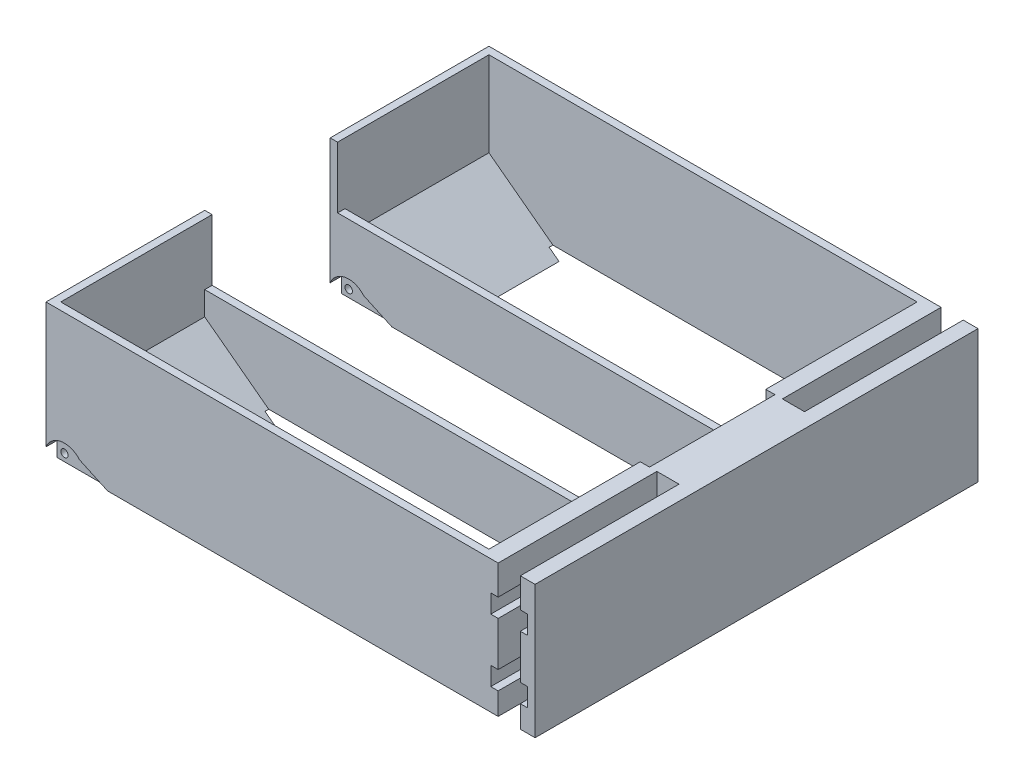
SolidWorks part; units mm, degrees
ref_plane "Front Plane" through (0, 0, 0) normal (0, 0, 1) x (1, 0, 0)
ref_plane "Top Plane" through (0, 0, 0) normal (0, 1, 0) x (1, 0, 0)
ref_plane "Right Plane" through (0, 0, 0) normal (1, 0, 0) x (0, 0, -1)
sketch "Sketch2" plane through (0, 0, 0) normal (0, 1, 0) x (1, 0, 0)
  line L1 (-60, -21.5) -> (60, -21.5)
  line L2 (-60, -21.5) -> (-60, 21.5)
  line L3 (-60, 21.5) -> (60, 21.5)
  line L4 (60, -21.5) -> (60, 21.5)
  line L5 (-60, -21.5) -> (60, 21.5) construction
  line L6 (-60, 21.5) -> (60, -21.5) construction
  point P0 (0, 0)
  dimension "D1" = 120
  dimension "D2" = 43
extrude "Boss-Extrude1" add sketch "Sketch2" along normal blind 38 contours L2 L3 L4 L1
sketch "Sketch3" plane through (0, 38, 0) normal (0, 1, 0) x (1, 0, 0)
  line L0 (-60, 21.5) -> (60, 21.5) construction
  line L1 (-58, -19.5) -> (58, -19.5)
  line L2 (-58, -19.5) -> (-58, 19.5)
  line L3 (-58, 19.5) -> (58, 19.5)
  line L4 (58, -19.5) -> (58, 19.5)
  line L5 (-58, -19.5) -> (58, 19.5) construction
  line L6 (-58, 19.5) -> (58, -19.5) construction
  line L7 (60, -21.5) -> (60, 21.5) construction
  point P0 (0, 0)
  dimension "D1" = 2
  dimension "D2" = 2
extrude "Cut-Extrude1" cut sketch "Sketch3" against normal up to vertex (38 mm away) up to point (-60, 0, -21.5)
sketch "Sketch4" plane through (0, 0, -19.5) normal (0, 0, 1) x (1, 0, 0)
  line L0 (-58, 0) -> (-58, 15)
  line L1 (-58, 15) -> (-38, 0)
  line L2 (-60, 0) -> (60, 0) construction
  line L3 (-38, 0) -> (-58, 0)
  dimension "D1" = 15
  dimension "D2" = 20
extrude "Boss-Extrude2" add sketch "Sketch4" along normal up to vertex (39 mm away) up to point (-58, 0, 19.5)
sketch "Sketch5" plane through (60, 0, 0) normal (1, 0, 0) x (0, 0, -1)
  line L1 (-21.5, 38) -> (21.5, 38)
  line L2 (-21.5, 38) -> (-21.5, 0)
  line L3 (-21.5, 0) -> (21.5, 0)
  line L4 (21.5, 38) -> (21.5, 0)
extrude "Boss-Extrude3" add sketch "Sketch5" along normal blind 2.5
sketch "Sketch6" plane through (0, 0, -21.5) normal (0, 0, -1) x (-1, 0, 0)
  line L0 (60, 0) -> (-62.5, 0) construction
  line L1 (-62.5, 38) -> (-60.5, 38)
  line L2 (-62.5, 38) -> (-62.5, 0)
  line L3 (-62.5, 0) -> (-60.5, 0)
  line L4 (-60.5, 38) -> (-60.5, 0)
  dimension "D1" = 2
extrude "Boss-Extrude4" add sketch "Sketch6" along normal blind 17 contours L4 L3 L2 L1
ref_plane "Plane1" through (0, 0, -38.5) normal (0, 0, -1) x (-1, 0, 0)
mirror "Mirror1" about plane through (0, 0, -38.5) normal (0, 0, -1) of bodies 105
sketch "Sketch7" plane through (62.5, 0, 0) normal (1, 0, 0) x (0, 0, -1)
  line L0 (38.5, 38) -> (38.5, 0) construction
  line L1 (98.5, 38) -> (-21.5, 38) construction
  line L2 (-21.5, 0) -> (98.5, 0) construction
  line L3 (-21.5, 19) -> (98.5, 19) construction
  line L4 (-21.5, 38) -> (-21.5, 0) construction
  line L5 (98.5, 38) -> (98.5, 0) construction
  line L11 (21.5, 0) -> (55.5, 0)
  line L12 (21.5, 0) -> (21.5, 38)
  line L13 (21.5, 38) -> (55.5, 38)
  line L14 (55.5, 0) -> (55.5, 38)
  line L15 (21.5, 0) -> (55.5, 38) construction
  line L16 (21.5, 38) -> (55.5, 0) construction
  point P12 (38.5, 19)
  point P13 (38.5, 19)
  dimension "D1" = 34
extrude "Boss-Extrude5" add sketch "Sketch7" along normal blind 10
sketch "Sketch8" plane through (0, 0, -21.5) normal (0, 0, 1) x (1, 0, 0)
  line L0 (72.5, 0) -> (62.5, 0) construction
  line L1 (72.5, 38) -> (68.5, 38)
  line L2 (72.5, 38) -> (72.5, 0)
  line L3 (72.5, 0) -> (68.5, 0)
  line L4 (68.5, 38) -> (68.5, 0)
  dimension "D1" = 4
extrude "Boss-Extrude6" add sketch "Sketch8" along normal up to vertex (43 mm away) up to point (62.5, 38, 21.5)
sketch "Sketch9" plane through (0, 0, 21.5) normal (0, 0, 1) x (1, 0, 0)
  line L0 (70.5, 38) -> (70.5, 0) construction
  line L1 (72.5, 38) -> (68.5, 38) construction
  line L2 (68.5, 0) -> (72.5, 0) construction
  line L3 (70.5, 19) -> (52.6863, 19) construction
  line L4 (70.5, 30) -> (60.5, 30)
  line L5 (70.5, 30) -> (70.5, 25)
  line L6 (70.5, 25) -> (60.5, 25)
  line L7 (60.5, 30) -> (60.5, 25)
  line L8 (70.5, 13) -> (60.5, 13)
  line L9 (60.5, 8) -> (60.5, 13)
  line L10 (70.5, 8) -> (60.5, 8)
  line L11 (70.5, 8) -> (70.5, 13)
  dimension "D1" = 10
  dimension "D2" = 5
  dimension "D3" = 25
extrude "Cut-Extrude2" cut sketch "Sketch9" against normal up to vertex (41 mm away) up to point (58, 38, -19.5)
mirror "Mirror2" about plane through (0, 0, -38.5) normal (0, 0, -1) of "Boss-Extrude6", "Cut-Extrude2"
sketch "Sketch11" plane through (72.5, 0, 0) normal (1, 0, 0) x (0, 0, -1)
  line L0 (98.5, 0) -> (98.5, 38) construction
  line L1 (-21.5, 0) -> (98.5, 0)
  line L2 (-21.5, 0) -> (-21.5, 2)
  line L3 (-21.5, 2) -> (98.5, 2)
  line L4 (98.5, 0) -> (98.5, 2)
  dimension "D1" = 2
extrude "Cut-Extrude3" cut sketch "Sketch11" against normal up to vertex (110.5 mm away) up to point (-38, 0, 19.5)
sketch "Sketch12" plane through (0, 0, 21.5) normal (0, 0, 1) x (1, 0, 0)
  line L0 (-60, 38) -> (-60, 0) construction
  line L1 (-38, 2) -> (-49.6148, 2)
  line L2 (-38, 2) -> (-38, 0)
  line L3 (-38, 0) -> (-60, 0)
  arc A0 (-49.6148, 2) -> (-60, 0) centre (-55, 2) ccw
  dimension "D1" = 5
extrude "Cut-Extrude4" cut sketch "Sketch12" against normal blind 3
ref_plane "Plane2" through (0, 0, 0) normal (0, 0, 1) x (1, 0, 0)
mirror "Mirror3" about plane through (0, 0, 0) normal (0, 0, 1) of "Cut-Extrude4"
mirror "Mirror4" about plane through (0, 0, -38.5) normal (0, 0, -1) of "Mirror3", "Cut-Extrude4"
sketch "Sketch13" plane through (0, 0, 18.5) normal (0, 0, 1) x (1, 0, 0)
  line L0 (-60, 0) -> (-38, 0) construction
  line L1 (-60, 0) -> (-60, 4) construction
  circle A0 centre (-58, 2) radius 1
  dimension "D1" = 2
  dimension "D2" = 2
  dimension "D3" = 2
extrude "Cut-Extrude5" cut sketch "Sketch13" against normal up to vertex (117 mm away) up to point (-60, 4, -98.5)
chamfer "Chamfer1" distance 10 angle 45 1 edges at (-49.6148, 2, 20)
chamfer "Chamfer2" distance 10 angle 45 1 edges at (-49.6148, 2, -20)
chamfer "Chamfer3" distance 10 angle 45 1 edges at (-49.6148, 2, -57)
chamfer "Chamfer4" distance 10 angle 45 1 edges at (-49.6148, 2, -97)
sketch "Sketch14" plane through (0, 38, 0) normal (0, 1, 0) x (1, 0, 0)
  line L0 (-60, 21.5) -> (60.5, 21.5) construction
  line L1 (-58, 19.5) -> (58, 19.5)
  line L2 (-58, 19.5) -> (-58, 21.5)
  line L3 (-58, 21.5) -> (58, 21.5)
  line L4 (58, 19.5) -> (58, 21.5)
  dimension "D1" = 116
extrude "Cut-Extrude6" cut sketch "Sketch14" against normal blind 16.6
mirror "Mirror5" about plane through (0, 0, -38.5) normal (0, 0, -1) of "Cut-Extrude6"
